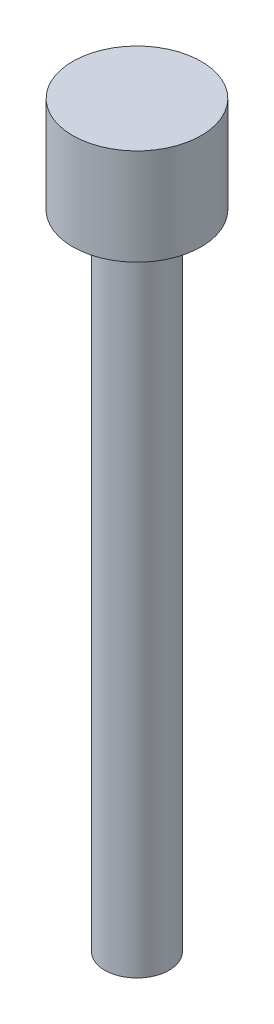
SolidWorks part; units mm, degrees
ref_plane "Front Plane" through (0, 0, 0) normal (0, 0, 1) x (1, 0, 0)
ref_plane "Top Plane" through (0, 0, 0) normal (0, 1, 0) x (1, 0, 0)
ref_plane "Right Plane" through (0, 0, 0) normal (1, 0, 0) x (0, 0, -1)
sketch "Sketch1" plane through (0, 0, 0) normal (0, 1, 0) x (1, 0, 0)
  circle A0 centre (0, 0) radius 1
  circle A1 centre (0, 0) radius 2
  dimension "D1" = 2
  dimension "D2" = 4
extrude "Boss-Extrude1" add sketch "Sketch1" along normal blind 3 contours A1
extrude "Boss-Extrude2" add sketch "Sketch1<3>" against normal blind 20 contours A0
sketch "Sketch1<3>" plane through (0, 0, 0) normal (0, 1, 0) x (1, 0, 0) same geometry as "Sketch1"
equation "\"D1@Sketch1\"=2mm"
equation "\"D1@Boss-Extrude1\"=3mm"
equation "\"D1@Boss-Extrude2\"=20mm"
equation "\"D2@Sketch1\"=4mm"
